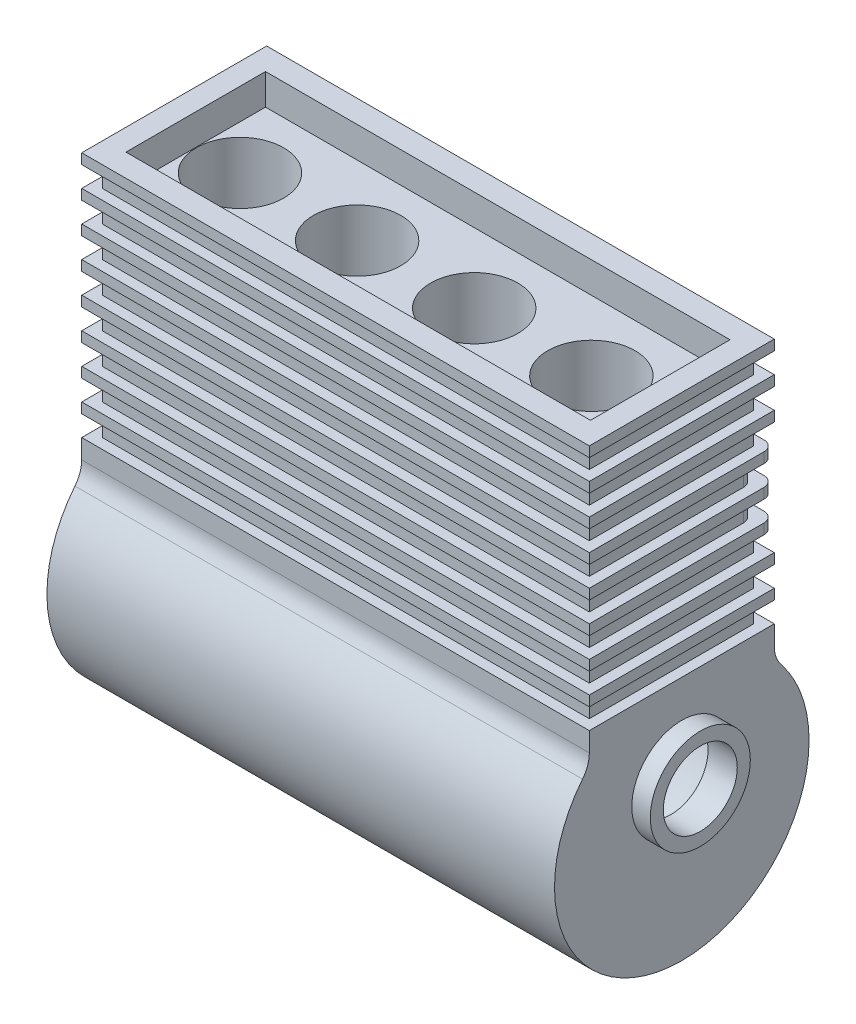
SolidWorks part; units mm, degrees
ref_plane "Front Plane" through (0, 0, 0) normal (0, 0, 1) x (1, 0, 0)
ref_plane "Top Plane" through (0, 0, 0) normal (0, 1, 0) x (1, 0, 0)
ref_plane "Right Plane" through (0, 0, 0) normal (1, 0, 0) x (0, 0, -1)
sketch "Sketch1" plane through (0, 0, 0) normal (0, 1, 0) x (1, 0, 0)
  line L1 (-254.5, 90) -> (254.5, 90)
  line L2 (-254.5, 90) -> (-254.5, -90)
  line L3 (-254.5, -90) -> (254.5, -90)
  line L4 (254.5, 90) -> (254.5, -90)
  line L5 (-254.5, 90) -> (254.5, -90) construction
  line L6 (-254.5, -90) -> (254.5, 90) construction
  point P0 (0, 0)
  dimension "D1" = 509
  dimension "D2" = 180
extrude "Boss-Extrude2" add sketch "Sketch1" along normal blind 200
sketch "Sketch2" plane through (0, 200, 0) normal (0, 1, 0) x (1, 0, 0)
  line L0 (-254.5, 0) -> (254.5, 0) construction
  line L1 (-254.5, 90) -> (-254.5, -90) construction
  line L2 (254.5, -90) -> (254.5, 90) construction
  line L3 (-254.5, 0) -> (-190.5, 0)
  line L4 (-190.5, 0) -> (-76.5, 0)
  line L5 (-76.5, 0) -> (37.5, 0)
  line L6 (37.5, 0) -> (151.5, 0)
  circle A0 centre (-190.5, 0) radius 42.5
  circle A1 centre (-76.5, 0) radius 42.5
  circle A2 centre (37.5, 0) radius 42.5
  circle A3 centre (151.5, 0) radius 42.5
sketch "Sketch3" plane through (0, 200, 0) normal (0, 1, 0) x (1, 0, 0)
  line L0 (254.5, 90) -> (239.5, 90)
  line L4 (254.5, 90) -> (-254.5, 90) construction
  line L6 (239.5, 90) -> (239.5, -90)
  line L7 (-254.5, -90) -> (254.5, -90) construction
  line L9 (254.5, 90) -> (254.5, -90)
  dimension "D1" = 15
extrude "Cut-Extrude2" cut sketch "Sketch3" against normal blind 200 and the other way through all
extrude "Cut-Extrude4" cut sketch "Sketch2" against normal through all contours L4 A0 L3 | L3 A0 L4 | L5 A1 L4 | L4 A1 L5 | L6 A2 L5 | L5 A2 L6 | L6 L0 A3 | L0 L6 A3
sketch "Sketch4" plane through (0, 0, 90) normal (0, 0, 1) x (1, 0, 0)
  line L0 (-254.5, 195) -> (-254.5, 175)
  line L1 (-254.5, 200) -> (-254.5, 0) construction
  line L2 (-254.5, 195) -> (-244.5, 195)
  line L3 (-244.5, 195) -> (-244.5, 175)
  line L4 (-244.5, 175) -> (-254.5, 175)
  line L5 (-254.5, 165) -> (-254.5, 145)
  line L6 (-254.5, 165) -> (-244.5, 165)
  line L7 (-244.5, 165) -> (-244.5, 145)
  line L8 (-244.5, 145) -> (-254.5, 145)
  line L9 (-254.5, 135) -> (-254.5, 115)
  line L10 (-254.5, 135) -> (-244.5, 135)
  line L11 (-244.5, 135) -> (-244.5, 115)
  line L12 (-244.5, 115) -> (-254.5, 115)
  line L13 (-254.5, 105) -> (-254.5, 85)
  line L14 (-254.5, 105) -> (-244.5, 105)
  line L15 (-244.5, 105) -> (-244.5, 85)
  line L16 (-244.5, 85) -> (-254.5, 85)
  line L17 (-254.5, 75) -> (-254.5, 55)
  line L18 (-254.5, 75) -> (-244.5, 75)
  line L19 (-244.5, 75) -> (-244.5, 55)
  line L20 (-244.5, 55) -> (-254.5, 55)
  line L21 (-254.5, 55) -> (-254.5, 195)
  line M10 (-254.5, 200) -> (-254.5, 0)
sketch "Sketch5" plane through (0, 0, 90) normal (0, 0, 1) x (1, 0, 0)
  line L0 (-244.5, 195) -> (239.5, 195) construction
  line L1 (239.5, 200) -> (239.5, 0) construction
sketch "Sketch6" plane through (239.5, 0, 0) normal (1, 0, 0) x (0, 0, -1)
  line L0 (-90, 195) -> (-80, 195)
  line L1 (-90, 55) -> (-90, 195) construction
  line L2 (-80, 195) -> (-80, 175)
  line L3 (-80, 175) -> (-90, 175)
  line L5 (-90, 165) -> (-80, 165)
  line L6 (-80, 165) -> (-80, 145)
  line L7 (-80, 145) -> (-90, 145)
  line L9 (-90, 135) -> (-80, 135)
  line L10 (-80, 135) -> (-80, 115)
  line L11 (-80, 115) -> (-90, 115)
  line L13 (-90, 105) -> (-80, 105)
  line L14 (-80, 105) -> (-80, 85)
  line L15 (-80, 85) -> (-90, 85)
  line L17 (-90, 75) -> (-80, 75)
  line L18 (-80, 75) -> (-80, 55)
  line L19 (-80, 55) -> (-90, 55)
  line L20 (-90, 200) -> (-90, 0) construction
  line L21 (-90, 55) -> (-90, 75)
  line L22 (-90, 85) -> (-90, 105)
  line L23 (-90, 115) -> (-90, 135)
  line L24 (-90, 145) -> (-90, 165)
  line L25 (-90, 175) -> (-90, 195)
sketch "Sketch12" plane through (0, 0, 90) normal (0, 0, 1) x (1, 0, 0)
  line L0 (239.5, 195) -> (229.5, 195)
  line L1 (229.5, 195) -> (229.5, 175)
  line L2 (229.5, 175) -> (239.5, 175)
  line L3 (239.5, 200) -> (239.5, 0) construction
  line L5 (239.5, 165) -> (229.5, 165)
  line L6 (229.5, 165) -> (229.5, 145)
  line L7 (229.5, 145) -> (239.5, 145)
  line L9 (239.5, 135) -> (229.5, 135)
  line L10 (229.5, 135) -> (229.5, 115)
  line L11 (229.5, 115) -> (239.5, 115)
  line L13 (239.5, 105) -> (229.5, 105)
  line L14 (229.5, 105) -> (229.5, 85)
  line L15 (229.5, 85) -> (239.5, 85)
  line L17 (239.5, 75) -> (229.5, 75)
  line L18 (229.5, 75) -> (229.5, 55)
  line L19 (229.5, 55) -> (239.5, 55)
  line L20 (239.5, 195) -> (239.5, 175)
  line L21 (239.5, 165) -> (239.5, 145)
  line L22 (239.5, 135) -> (239.5, 115)
  line L23 (239.5, 105) -> (239.5, 85)
  line L24 (239.5, 75) -> (239.5, 55)
extrude "Cut-Extrude10" cut sketch "Sketch6" against normal through all
extrude "Cut-Extrude11" cut sketch "Sketch12" against normal through all
extrude "Cut-Extrude12" cut sketch "Sketch4" against normal through all contours L4 L3 L2 M10 | L8 L7 L6 M10 | L16 L15 L14 M10 | L20 L19 L18 M10 | L9 L12 L11 L10
mirror "Mirror3" about plane through (0, 0, 0) normal (0, 0, 1) of "Cut-Extrude10"
fillet "Fillet1" radius 10 3 edges at (239.5, 170, -90) (229.5, 185, -80) (239.5, 197.5, -90)
sketch "Sketch16" plane through (239.5, 0, 0) normal (1, 0, 0) x (0, 0, -1)
  line L0 (90, 0) -> (-90, 0) construction
  circle A0 centre (0, 0) radius 36
sketch "Sketch17" plane through (0, 0, 0) normal (0, -1, 0) x (1, 0, 0)
  line L0 (-254.5, 90) -> (239.5, -90)
  line L1 (239.5, -90) -> (239.5, 90)
  line L2 (239.5, 90) -> (-254.5, -90)
  line L4 (-233.5533, 67.9042) -> (218.5533, 67.9042)
  line L5 (-233.5533, 67.9042) -> (-233.5533, -67.9042)
  line L6 (-233.5533, -67.9042) -> (218.5533, -67.9042)
  line L7 (218.5533, 67.9042) -> (218.5533, -67.9042)
  line L8 (-233.5533, 67.9042) -> (218.5533, -67.9042) construction
  line L9 (-233.5533, -67.9042) -> (218.5533, 67.9042) construction
  point P4 (-7.5, 0)
extrude "Cut-Extrude14" cut sketch "Sketch17" against normal blind 105 contours L5 L4 L7 L6
extrude "Cut-Extrude15" cut sketch "Sketch16" against normal through all
sketch "Sketch19" plane through (0, 0, 0) normal (0, -1, 0) x (1, 0, 0)
  line L0 (-244.1358, 79.0746) -> (229.1358, 79.0746)
  line L1 (-244.1358, 79.0746) -> (-244.1358, -79.6625)
  line L2 (229.1358, 79.0746) -> (229.1358, -79.6625)
  line L3 (-244.1358, -79.6625) -> (229.1358, -79.6625)
extrude "Cut-Extrude16" cut sketch "Sketch19" against normal blind 47
mirror "Mirror10" about plane through (0, 200, 0) normal (0, 1, 0) of bodies 122
sketch "Sketch22" plane through (0, 400, 0) normal (0, 1, 0) x (1, 0, 0)
  line L0 (-254.5, -90) -> (239.5, -90)
  line L1 (-254.5, -90) -> (-254.5, 89.657)
  line L2 (239.5, -90) -> (239.5, 89.657)
  line L3 (-254.5, 89.657) -> (239.5, 89.657)
  line L4 (-244.5, -90) -> (239.5, -90) construction
extrude "Cut-Extrude20" cut sketch "Sketch22" against normal blind 75
sketch "Sketch23" plane through (0, 0, 0) normal (0, -1, 0) x (1, 0, 0)
  line L0 (-244.1358, -0.294) -> (-244.1358, 84.9537) construction
  line L1 (-244.1358, 79.0746) -> (-244.1358, -79.6625) construction
  line L2 (-244.1358, 84.9537) -> (228.5479, 84.9537) construction
  line L3 (228.5479, 84.9537) -> (228.5479, -84.9537) construction
  line L4 (228.5479, -84.9537) -> (-244.1358, -84.9537) construction
  line L5 (-244.1358, -84.9537) -> (-244.1358, -0.294) construction
  line L6 (-244.1358, 84.9537) -> (228.5479, 84.9537)
  line L7 (-244.1358, 84.9537) -> (-244.1358, -84.9537)
  line L8 (228.5479, 84.9537) -> (228.5479, -84.9537)
  line L9 (-244.1358, -84.9537) -> (228.5479, -84.9537)
extrude "Cut-Extrude21" cut sketch "Sketch23" against normal blind 51
sketch "Sketch27" plane through (0, 0, -84.9537) normal (0, 0, 1) x (1, 0, 0)
  line L1 (-244.1358, 0) -> (228.5966, 0)
  line L2 (-244.1358, 0) -> (-244.1358, 50.9971)
  line L3 (-244.1358, 50.9971) -> (228.5966, 50.9971)
  line L4 (228.5966, 0) -> (228.5966, 50.9971)
extrude "Cut-Extrude22" cut sketch "Sketch27" along normal blind 189 and the other way blind 33
sketch "Sketch28" plane through (239.5, 0, 0) normal (1, 0, 0) x (0, 0, -1)
  line L0 (-90, 55) -> (90, 55)
  arc A0 (-90, 55) -> (90, 55) centre (0, -30.0895) ccw
  arc M3 (-36, 0) -> (36, 0) centre (0, 0) cw
  line M4 (36, 0) -> (90, 0)
  line M5 (90, 0) -> (90, 55)
  line M7 (-90, 55) -> (-90, 0)
  line M8 (-90, 0) -> (-36, 0)
extrude "Boss-Extrude5" add sketch "Sketch28" against normal blind 494 contours A0 M7 M5 M4 M3 M8
sketch "Sketch30" plane through (239.5, 0, 0) normal (1, 0, 0) x (0, 0, -1)
  circle A0 centre (0, 0) radius 36
extrude "Cut-Extrude24" cut sketch "Sketch30" against normal through all
ref_plane "Plane1" through (-7.5, 0, 0) normal (-1, 0, 0) x (0, 0, 1)
sketch "Sketch31" plane through (-7.5, 0, 0) normal (-1, 0, 0) x (0, 0, 1)
  line L0 (-80.4054, 46.5333) -> (80.4054, 46.5333)
  arc A0 (-80.4054, 46.5333) -> (80.4054, 46.5333) centre (0, -30.0895) ccw
extrude "Cut-Extrude25" cut sketch "Sketch31" against normal mid plane 473
sketch "Sketch35" plane through (-244.5, 0, 0) normal (-1, 0, 0) x (0, 0, 1)
  line L1 (80, 55) -> (90, 55)
  line L2 (80, 55) -> (80, 75)
  line L3 (80, 75) -> (90, 75)
  line L4 (90, 55) -> (90, 75)
extrude "Boss-Extrude10" add sketch "Sketch35" against normal blind 484 and the other way blind 10
sketch "Sketch38" plane through (-244.5, 0, 0) normal (-1, 0, 0) x (0, 0, 1)
  line L1 (-80, 55) -> (-90, 55)
  line L2 (-80, 55) -> (-80, 75)
  line L3 (-80, 75) -> (-90, 75)
  line L4 (-90, 55) -> (-90, 75)
extrude "Boss-Extrude11" add sketch "Sketch38" against normal blind 484 and the other way blind 10
sketch "Sketch39" plane through (0, 0, 80) normal (0, 0, -1) x (-1, 0, 0)
  line L0 (244.5, 75) -> (244.5, 55) construction
  line L1 (244.5, 75) -> (254.5, 75)
  line L2 (244.5, 75) -> (244.5, 55)
  line L3 (244.5, 55) -> (254.5, 55)
  line L4 (254.5, 75) -> (254.5, 55)
sketch "Sketch40" plane through (-244.5, 0, 0) normal (-1, 0, 0) x (0, 0, 1)
  line L1 (-80, 75) -> (80, 75)
  line L2 (-80, 75) -> (-80, 55)
  line L3 (-80, 55) -> (80, 55)
  line L4 (80, 75) -> (80, 55)
extrude "Cut-Extrude26" cut sketch "Sketch40" against normal blind 484
sketch "Sketch41" plane through (0, 55, 0) normal (0, 1, 0) x (1, 0, 0)
  line L1 (229, 111.0679) -> (229, -111.0679) construction
  line L2 (-244, 80.1287) -> (229, 80.1287)
  line L3 (-244, 80.1287) -> (-244, -80.1287)
  line L4 (-244, -80.1287) -> (229, -80.1287)
  line L5 (229, 80.1287) -> (229, -80.1287)
  point P2 (-7.5, 0)
extrude "Cut-Extrude27" cut sketch "Sketch41" against normal blind 29
extrude "Boss-Extrude12" add sketch "Sketch39" along normal up to vertex (160 mm away)
sketch "Sketch43" plane through (0, 0, 80) normal (0, 0, -1) x (-1, 0, 0)
  line L0 (-229, 55) -> (-229, 75)
  line L1 (244.5, 75) -> (-239.5, 75) construction
  line L2 (-229, 75) -> (-239.5, 75)
  line L3 (-239.5, 75) -> (-239.5, 55)
  line L4 (-239.5, 55) -> (-229, 55)
extrude "Boss-Extrude13" add sketch "Sketch43" along normal up to vertex (160 mm away)
fillet "Fillet5" radius 30 1 edges at (-7.5, 55, 90)
fillet "Fillet6" radius 30 1 edges at (-7.5, 55, -90)
fillet "Fillet7" radius 10 1 edges at (-7.5, 75, -67.9042)
fillet "Fillet8" radius 10 1 edges at (-7.5, 75, 67.9042)
fillet "Fillet9" radius 4.9 2 edges at (-7.7261, 51, 80.1287) (-7.7261, 51, -80.1287)
sketch "Sketch44" plane through (239.5, 0, 0) normal (1, 0, 0) x (0, 0, -1)
  circle A0 centre (0, 0) radius 48.6832
  circle A1 centre (0, 0) radius 36
extrude "Boss-Extrude14" add sketch "Sketch44" along normal blind 18
sketch "Sketch45" plane through (-254.5, 0, 0) normal (-1, 0, 0) x (0, 0, 1)
  circle A0 centre (0, 0) radius 51.2722
  circle A1 centre (0, 0) radius 36
extrude "Boss-Extrude15" add sketch "Sketch45" along normal blind 15
